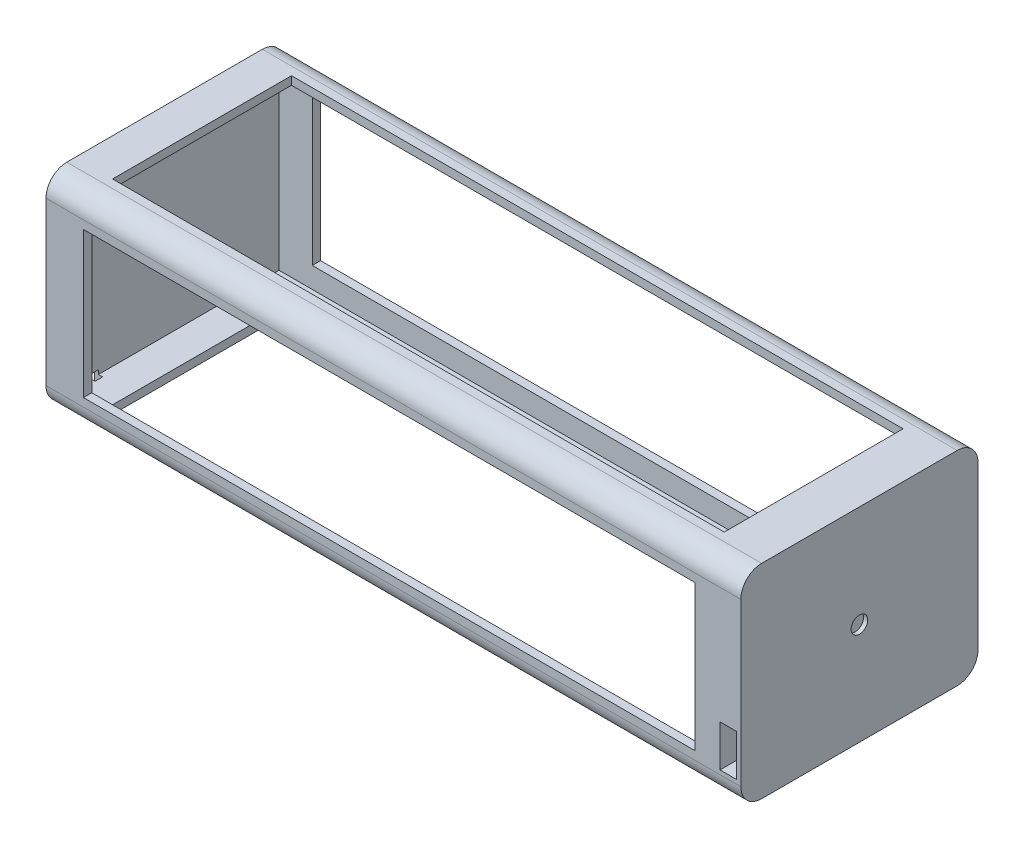
SolidWorks part; units mm, degrees
material "PET"
ref_plane "Спереди" through (0, 0, 0) normal (0, 0, 1) x (1, 0, 0)
ref_plane "Сверху" through (0, 0, 0) normal (0, 1, 0) x (1, 0, 0)
ref_plane "Справа" through (0, 0, 0) normal (1, 0, 0) x (0, 0, -1)
sketch "Эскиз1" plane through (0, 0, 0) normal (1, 0, 0) x (0, 0, -1)
  line L1 (26.5, -22.5) -> (-26.5, -22.5)
  line L2 (26.5, -22.5) -> (26.5, 22.5)
  line L3 (26.5, 22.5) -> (-26.5, 22.5)
  line L4 (-26.5, -22.5) -> (-26.5, 22.5)
  line L5 (26.5, -22.5) -> (-26.5, 22.5) construction
  line L6 (26.5, 22.5) -> (-26.5, -22.5) construction
  line L7 (28.5, -24.5) -> (-28.5, -24.5)
  line L8 (28.5, -24.5) -> (28.5, 24.5)
  line L9 (28.5, 24.5) -> (-28.5, 24.5)
  line L10 (-28.5, -24.5) -> (-28.5, 24.5)
  line L11 (28.5, -24.5) -> (-28.5, 24.5) construction
  line L12 (28.5, 24.5) -> (-28.5, -24.5) construction
  point P0 (0, 0)
  point P6 (0, 0)
  dimension "D1" = 53
  dimension "D2" = 45
  dimension "D3" = 57
  dimension "D4" = 49
extrude "Бобышка-Вытянуть1" add sketch "Эскиз1" against normal blind 5
ref_plane "Плоскость4" through (-5, 0, 0) normal (1, 0, 0) x (0, 0, -1)
sketch "Эскиз2" plane through (-5, 0, 0) normal (1, 0, 0) x (0, 0, -1)
  line L0 (26.5, 22.5) -> (-26.5, 22.5) construction
  line L1 (28.5, 24.5) -> (21.5, 24.5)
  line L2 (28.5, 24.5) -> (28.5, 22.5)
  line L3 (26.5, 22.5) -> (21.5, 22.5)
  line L4 (21.5, 24.5) -> (21.5, 22.5)
  line L5 (26.5, -22.5) -> (26.5, 22.5) construction
  line L6 (28.5, 24.5) -> (26.5, 24.5)
  line L7 (28.5, 24.5) -> (28.5, 17.5)
  line L8 (28.5, 17.5) -> (26.5, 17.5)
  line L9 (26.5, 22.5) -> (26.5, 17.5)
  line L10 (0, 34.0761) -> (0, -34.0192) construction
  line L11 (38.3689, 0) -> (-37.9997, 0) construction
  line L12 (-28.5, 24.5) -> (-28.5, 17.5)
  line L13 (-28.5, 17.5) -> (-26.5, 17.5)
  line L14 (-26.5, 22.5) -> (-26.5, 17.5)
  line L15 (-26.5, 22.5) -> (-21.5, 22.5)
  line L16 (-21.5, 24.5) -> (-21.5, 22.5)
  line L17 (-28.5, 24.5) -> (-21.5, 24.5)
  line L18 (-28.5, -24.5) -> (-21.5, -24.5)
  line L19 (-21.5, -24.5) -> (-21.5, -22.5)
  line L20 (-26.5, -22.5) -> (-21.5, -22.5)
  line L21 (-26.5, -22.5) -> (-26.5, -17.5)
  line L22 (-28.5, -17.5) -> (-26.5, -17.5)
  line L23 (-28.5, -24.5) -> (-28.5, -17.5)
  line L24 (28.5, -24.5) -> (28.5, -17.5)
  line L25 (28.5, -17.5) -> (26.5, -17.5)
  line L26 (26.5, -22.5) -> (26.5, -17.5)
  line L27 (26.5, -22.5) -> (21.5, -22.5)
  line L28 (21.5, -24.5) -> (21.5, -22.5)
  line L29 (28.5, -24.5) -> (21.5, -24.5)
  dimension "D1" = 7
  dimension "D2" = 7
extrude "Бобышка-Вытянуть2" add sketch "Эскиз2" against normal blind 147 contours L17 L12 L13 L14 L15 L16 | L23 L18 L19 L20 L21 L22 | L1 L4 L3 L9 L8 L7 | L27 L28 L29 L24 L25 L26 region at (-5, 24.401, 25) region at (-5, -21, 28.401)
ref_plane "Плоскость5" through (-152, 0, 0) normal (1, 0, 0) x (0, 0, -1)
sketch "Эскиз3" plane through (-152, 0, 0) normal (1, 0, 0) x (0, 0, -1)
  line L1 (-26.5, -22.5) -> (26.5, -22.5)
  line L2 (-26.5, -22.5) -> (-26.5, 22.5)
  line L3 (-26.5, 22.5) -> (26.5, 22.5)
  line L4 (26.5, -22.5) -> (26.5, 22.5)
  line L5 (-26.5, -22.5) -> (26.5, 22.5) construction
  line L6 (-26.5, 22.5) -> (26.5, -22.5) construction
  line L7 (-28.5, -24.5) -> (28.5, -24.5)
  line L8 (-28.5, -24.5) -> (-28.5, 24.5)
  line L9 (-28.5, 24.5) -> (28.5, 24.5)
  line L10 (28.5, -24.5) -> (28.5, 24.5)
  line L11 (-28.5, -24.5) -> (28.5, 24.5) construction
  line L12 (-28.5, 24.5) -> (28.5, -24.5) construction
  point P0 (0, 0)
  point P7 (0, 0)
extrude "Бобышка-Вытянуть3" add sketch "Эскиз3" against normal blind 8
sketch "Эскиз5" plane through (0, 0, 0) normal (1, 0, 0) x (0, 0, -1)
  line L1 (28.5, -24.5) -> (-28.5, -24.5)
  line L2 (28.5, -24.5) -> (28.5, 24.5)
  line L3 (28.5, 24.5) -> (-28.5, 24.5)
  line L4 (-28.5, -24.5) -> (-28.5, 24.5)
  line L5 (28.5, -24.5) -> (-28.5, 24.5) construction
  line L6 (28.5, 24.5) -> (-28.5, -24.5) construction
  point P0 (0, 0)
extrude "Бобышка-Вытянуть4" add sketch "Эскиз5" along normal blind 1
sketch "Эскиз7" plane through (-160, 0, 0) normal (-1, 0, 0) x (0, 0, 1)
  line L1 (28.5, -24.5) -> (-28.5, -24.5)
  line L2 (28.5, -24.5) -> (28.5, 24.5)
  line L3 (28.5, 24.5) -> (-28.5, 24.5)
  line L4 (-28.5, -24.5) -> (-28.5, 24.5)
  line L5 (28.5, -24.5) -> (-28.5, 24.5) construction
  line L6 (28.5, 24.5) -> (-28.5, -24.5) construction
  point P0 (0, 0)
extrude "Бобышка-Вытянуть6" add sketch "Эскиз7" along normal blind 1
sketch "Эскиз8" plane through (-161, 0, 0) normal (-1, 0, 0) x (0, 0, 1)
  line L0 (-28.5, -24.5) -> (28.5, -24.5) construction
  line L1 (22.5, -24.5) -> (20.7, -24.5)
  line L2 (22.5, -24.5) -> (22.5, -21.5)
  line L3 (22.5, -21.5) -> (20.7, -21.5)
  line L4 (20.7, -24.5) -> (20.7, -21.5)
  line L6 (18.7, -24.5) -> (16.9, -24.5)
  line L7 (18.7, -24.5) -> (18.7, -21.5)
  line L8 (18.7, -21.5) -> (16.9, -21.5)
  line L9 (16.9, -24.5) -> (16.9, -21.5)
  line L10 (14.9, -24.5) -> (14.4, -24.5)
  line L11 (14.9, -24.5) -> (14.9, -23)
  line L12 (14.9, -23) -> (14.4, -23)
  line L13 (14.4, -24.5) -> (14.4, -23)
  line L14 (13.4, -24.5) -> (12.9, -24.5)
  line L15 (13.4, -24.5) -> (13.4, -23)
  line L16 (13.4, -23) -> (12.9, -23)
  line L17 (12.9, -24.5) -> (12.9, -23)
  line L18 (11.9, -24.5) -> (11.4, -24.5)
  line L19 (11.9, -24.5) -> (11.9, -23)
  line L20 (11.9, -23) -> (11.4, -23)
  line L21 (11.4, -24.5) -> (11.4, -23)
  line L22 (10.4, -24.5) -> (9.9, -24.5)
  line L23 (10.4, -24.5) -> (10.4, -23)
  line L24 (10.4, -23) -> (9.9, -23)
  line L25 (9.9, -24.5) -> (9.9, -23)
  line L26 (8.9, -24.5) -> (8.4, -24.5)
  line L27 (8.9, -24.5) -> (8.9, -23)
  line L28 (8.9, -23) -> (8.4, -23)
  line L29 (8.4, -24.5) -> (8.4, -23)
  line L30 (7.4, -24.5) -> (6.9, -24.5)
  line L31 (7.4, -24.5) -> (7.4, -23)
  line L32 (7.4, -23) -> (6.9, -23)
  line L33 (6.9, -24.5) -> (6.9, -23)
  line L34 (5.9, -24.5) -> (5.4, -24.5)
  line L35 (5.9, -24.5) -> (5.9, -23)
  line L36 (5.9, -23) -> (5.4, -23)
  line L37 (5.4, -24.5) -> (5.4, -23)
  dimension "D1" = 1.8
  dimension "D2" = 3
  dimension "D3" = 6
  dimension "D4" = 2
  dimension "D5" = 1
  dimension "D6" = 1
  dimension "D7" = 1
  dimension "D8" = 1
  dimension "D9" = 1
  dimension "D10" = 1
  dimension "D11" = 2
  dimension "D12" = 0.5
  dimension "D13" = 1.5
extrude "Вырез-Вытянуть1" cut sketch "Эскиз8" against normal blind 2
sketch "Эскиз9" plane through (1, 0, 0) normal (1, 0, 0) x (0, 0, -1)
  line L0 (28.5, 24.5) -> (-28.5, 24.5) construction
  line L1 (24.5, -20.5) -> (-24.5, -20.5)
  line L2 (24.5, -20.5) -> (24.5, 8.5)
  line L3 (24.5, 20.5) -> (-24.5, 20.5)
  line L4 (-24.5, -20.5) -> (-24.5, -18.5)
  line L5 (24.5, -20.5) -> (-24.5, 20.5) construction
  line L6 (24.5, 20.5) -> (-24.5, -20.5) construction
  line L7 (28.5, -24.5) -> (28.5, 24.5) construction
  line L8 (24.5, 18.5) -> (28.5, 18.5)
  line L9 (28.5, -24.5) -> (-28.5, -24.5)
  line L10 (28.5, -24.5) -> (28.5, 8.5)
  line L11 (28.5, 24.5) -> (-28.5, 24.5)
  line L12 (-28.5, -24.5) -> (-28.5, -18.5)
  line L13 (28.5, -24.5) -> (-28.5, 24.5) construction
  line L14 (28.5, 24.5) -> (-28.5, -24.5) construction
  line L15 (24.5, 8.5) -> (28.5, 8.5)
  line L16 (0, 32.8484) -> (0, -30.0594) construction
  line L17 (-33.5411, 0) -> (36.5459, 0) construction
  line L18 (24.5, 18.5) -> (24.5, 20.5)
  line L19 (28.5, 18.5) -> (28.5, 24.5)
  line L20 (1.3, -18.5) -> (-1.3, -18.5)
  line L21 (1.3, 8.5) -> (-1.3, 8.5)
  line L22 (1.3, 8.5) -> (1.3, 18.5)
  line L23 (1.3, 18.5) -> (-1.3, 18.5)
  line L24 (-1.3, 8.5) -> (-1.3, 18.5)
  line L25 (-1.3, -8.5) -> (-1.3, -18.5)
  line L26 (1.3, -8.5) -> (-1.3, -8.5)
  line L27 (1.3, -8.5) -> (1.3, -18.5)
  line L28 (-24.5, -8.5) -> (-28.5, -8.5)
  line L29 (-24.5, -18.5) -> (-28.5, -18.5)
  line L30 (-28.5, -8.5) -> (-28.5, 24.5)
  line L31 (-24.5, -8.5) -> (-24.5, 20.5)
  line L32 (-28.5, 24.5) -> (-28.5, -24.5) construction
  point P0 (0, 0)
  point P10 (0, 0)
  dimension "D1" = 4
  dimension "D2" = 4
  dimension "D3" = 10
  dimension "D4" = 6
  dimension "D5" = 2.6
  dimension "D6" = 10
  dimension "D7" = 8.5
  dimension "D8" = 1.3
extrude "Бобышка-Вытянуть7" add sketch "Эскиз9" along normal blind 4
sketch "Эскиз10" plane through (5, 0, 0) normal (1, 0, 0) x (0, 0, -1)
  line L1 (28.5, -24.5) -> (-28.5, -24.5)
  line L2 (28.5, -24.5) -> (28.5, 24.5)
  line L3 (28.5, 24.5) -> (-28.5, 24.5)
  line L4 (-28.5, -24.5) -> (-28.5, 24.5)
  line L5 (28.5, -24.5) -> (-28.5, 24.5) construction
  line L6 (28.5, 24.5) -> (-28.5, -24.5) construction
  point P0 (0, 0)
extrude "Бобышка-Вытянуть8" add sketch "Эскиз10" along normal blind 1
sketch "Эскиз11" plane through (6, 0, 0) normal (1, 0, 0) x (0, 0, -1)
  circle A0 centre (0, 0) radius 2
  dimension "D1" = 4
extrude "Вырез-Вытянуть2" cut sketch "Эскиз11" against normal blind 6
fillet "Скругление2" radius 5 4 edges at (-77.5, -24.5, 28.5) (-77.5, -24.5, -28.5) (-77.5, 24.5, -28.5) (-77.5, 24.5, 28.5)
